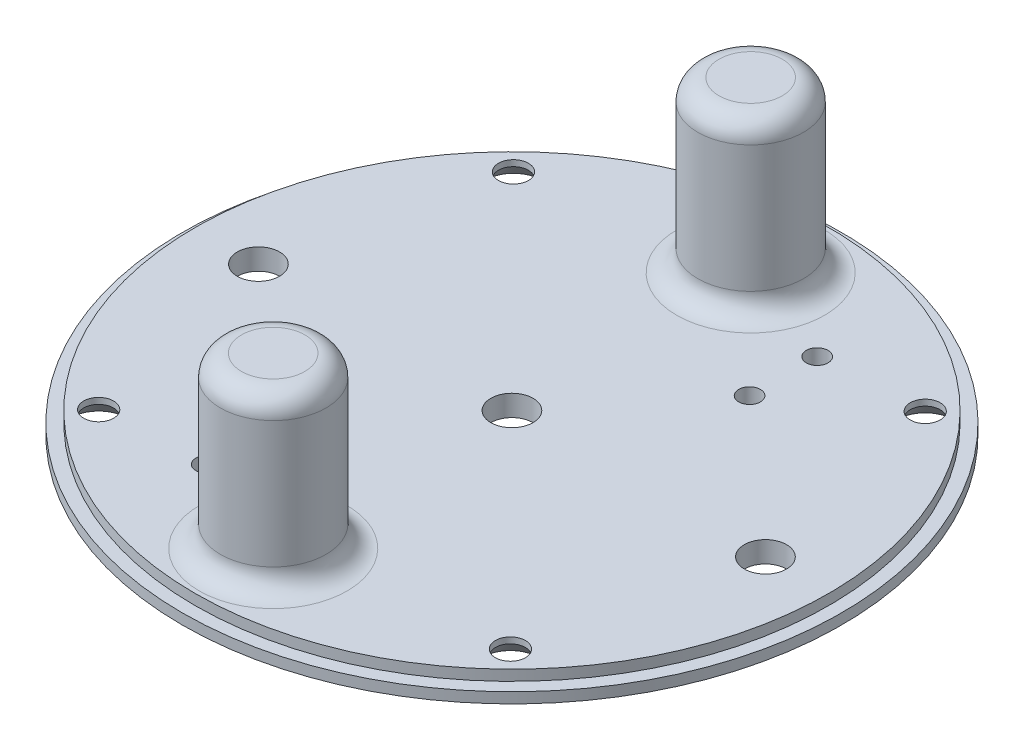
SolidWorks part; units mm, degrees
material "6061-T6 (SS)"
ref_plane "Front Plane" through (0, 0, 0) normal (0, 0, 1) x (1, 0, 0)
ref_plane "Top Plane" through (0, 0, 0) normal (0, 1, 0) x (1, 0, 0)
ref_plane "Right Plane" through (0, 0, 0) normal (1, 0, 0) x (0, 0, -1)
sketch "Sketch1" plane through (0, 0, 0) normal (0, 1, 0) x (1, 0, 0)
  circle A0 centre (0, 0) radius 49.53
  dimension "D1" = 99.06
extrude "Boss-Extrude1" add sketch "Sketch1" along normal blind 1.5875
sketch "Sketch2" plane through (0, 1.5875, 0) normal (0, 1, 0) x (1, 0, 0)
  circle A0 centre (0, 0) radius 47.625
  dimension "D1" = 95.25
extrude "Boss-Extrude2" add sketch "Sketch2" along normal blind 1.5875
sketch "Sketch3" plane through (0, 3.175, 0) normal (0, 1, 0) x (1, 0, 0)
  line L0 (-38.1, 0) -> (38.1, 0) construction
  circle A0 centre (-38.1, 0) radius 3.175
  circle A1 centre (38.1, 0) radius 3.175
  dimension "D1" = 6.35
  dimension "D2" = 6.35
  dimension "D3" = 76.2
extrude "Cut-Extrude1" cut sketch "Sketch3" against normal through all
sketch "Sketch4" plane through (0, 3.175, 0) normal (0, 1, 0) x (1, 0, 0)
  line L0 (-34.925, 0) -> (34.925, 0) construction
  line L1 (0, 47.625) -> (0, -47.625) construction
  circle A0 centre (-38.1, 0) radius 3.175 construction
  circle A1 centre (38.1, 0) radius 3.175 construction
  circle A2 centre (0, 0) radius 47.625 construction
  circle A3 centre (0, 0) radius 47.625 construction
sketch "Sketch5" plane through (0, 3.175, 0) normal (0, 1, 0) x (1, 0, 0)
  circle A0 centre (0, 0) radius 3.175
  dimension "D1" = 6.35
extrude "Cut-Extrude2" cut sketch "Sketch5" against normal through all
hole_wizard "CSK for #8 Flat Head Machine Screw2" positions "Sketch9" profile "Sketch8" countersink size "#8" standard "ANSI Inch" end condition through all
sketch "Sketch9" plane through (0, 0, 0) normal (0, -1, 0) x (-1, 0, 0)
  circle A0 centre (31.1698, -30.9406) radius 3.9624 construction
  point P0 (31.1698, -30.9406)
sketch "Sketch8" plane through (-31.1698, 0, 30.9406) normal (1, 0, 0) x (0, 0, -1)
  line L0 (0, 0) -> (0, 3.175)
  line L1 (0, 3.175) -> (2.2479, 3.175)
  line L2 (2.2479, 3.175) -> (2.2479, 2.2645)
  line L3 (2.2479, 2.2645) -> (4.2164, 0)
  line L5 (4.2164, 0) -> (0, 0)
  line L6 (-2.2479, 2.2645) -> (-4.2164, 0) construction
  line L11 (0, -6.35) -> (0, 107.95) construction
  dimension "Thru Hole Dia." = 4.4958
  dimension "Thru Hole Depth" = 3.175
  dimension "Near C'Sink Dia." = 8.4328
  dimension "Near C'Sink Angle" = 82
pattern_circular "CirPattern1" count 4 over 360 about axis through (0, 0, 0) along (0, 1, 0) of "CSK for #8 Flat Head Machine Screw2"
hole_wizard "#4 Clearance Hole1" positions "Sketch13" profile "Sketch12" hole size "#4" standard "ANSI Inch" end condition through all
sketch "Sketch13" plane through (0, 0, 0) normal (0, -1, 0) x (-1, 0, 0)
  line L0 (-15.9298, 29.9439) -> (-15.9298, 19.7839) construction
  line L2 (15.9298, -19.7839) -> (15.9298, -29.9439) construction
  line L5 (15.9298, -19.7839) -> (-15.9298, 19.7839) construction
  circle A0 centre (-31.1698, 30.9406) radius 2.2479 construction
  point P0 (-15.9298, 19.7839)
  point P2 (15.9298, -19.7839)
  point P4 (-15.9298, 29.9439)
  point P6 (15.9298, -29.9439)
  dimension "D3" = 15.24
  dimension "D1" = 10.16
  dimension "D2" = 10.16
  dimension "D5" = 25.4
sketch "Sketch12" plane through (15.9298, 0, -19.7839) normal (1, 0, 0) x (0, 0, -1)
  line L0 (0, 0) -> (0, 3.175)
  line L1 (0, 3.175) -> (1.6319, 3.175)
  line L2 (1.6319, 3.175) -> (1.6319, 0)
  line L5 (1.6319, 0) -> (0, 0)
  line L11 (0, -6.35) -> (0, 107.95) construction
  dimension "Thru Hole Dia." = 3.2639
  dimension "Thru Hole Depth" = 3.175
sketch "Sketch14" plane through (0, 3.175, 0) normal (0, 1, 0) x (1, 0, 0)
  line L0 (0, 47.625) -> (0, -47.625) construction
  line L1 (0, 35.8775) -> (0, -35.8775) construction
  circle A0 centre (0, 35.8775) radius 7.9375
  circle A1 centre (0, -35.8775) radius 7.9375
  dimension "D1" = 15.875
  dimension "D2" = 71.755
extrude "Boss-Extrude3" add sketch "Sketch14" along normal blind 25.4
sketch "Sketch15" plane through (0, 0, 0) normal (0, -1, 0) x (1, 0, 0)
  circle A0 centre (0, -35.8775) radius 6.35
  circle A1 centre (0, 35.8775) radius 6.35
  dimension "D1" = 12.7
extrude "Cut-Extrude3" cut sketch "Sketch15" against normal blind 26.9875
fillet "Fillet1" radius 3.175 6 edges at (0, 3.175, -27.94) (0, 3.175, 43.815) (0, 28.575, -27.94) (0, 28.575, 43.815) (0, 26.9875, 29.5275) (0, 26.9875, -42.2275)
